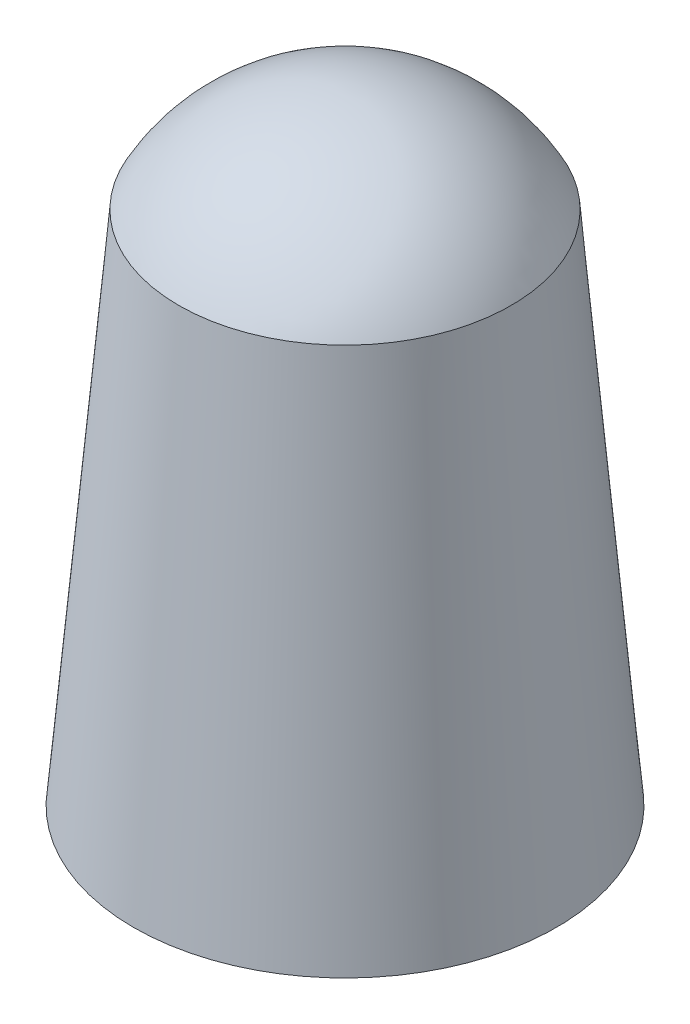
SolidWorks part; units mm, degrees
ref_plane "Front Plane" through (0, 0, 0) normal (0, 0, 1) x (1, 0, 0)
ref_plane "Top Plane" through (0, 0, 0) normal (0, 1, 0) x (1, 0, 0)
ref_plane "Right Plane" through (0, 0, 0) normal (1, 0, 0) x (0, 0, -1)
sketch "Sketch1" plane through (0, 0, 0) normal (0, 1, 0) x (1, 0, 0)
  circle A0 centre (0, 0) radius 5.4102
  dimension "D1" = 10.8204
extrude "Boss-Extrude1" add sketch "Sketch1" along normal blind 13.208 draft 5
dome "Dome1" faces to dome 1 distance 2.54 reverse direction no elliptical dome no face at (0, 13.208, 4.2546) parameters "D1"=2.54
